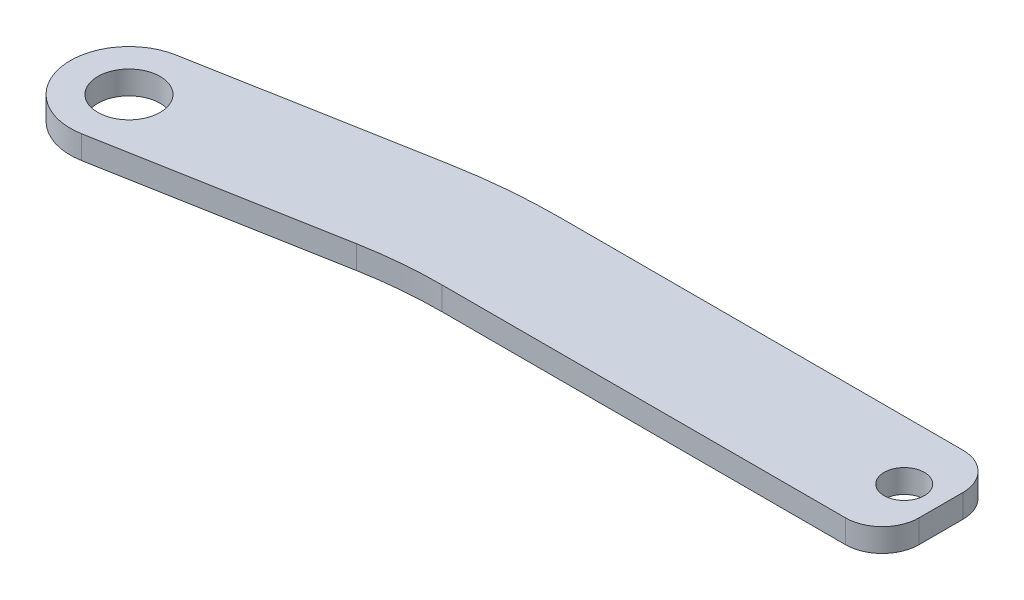
SolidWorks part; units mm, degrees
material "Copper"
ref_plane "Front Plane" through (0, 0, 0) normal (0, 0, 1) x (1, 0, 0)
ref_plane "Top Plane" through (0, 0, 0) normal (0, 1, 0) x (1, 0, 0)
ref_plane "Right Plane" through (0, 0, 0) normal (1, 0, 0) x (0, 0, -1)
sketch "Sketch1" plane through (0, 0, 0) normal (0, 1, 0) x (1, 0, 0)
  line L0 (-1.4287, 7.8714) -> (30.29, 13.6283)
  line L1 (43.8622, 14.85) -> (98.8622, 14.85)
  line L2 (98.8622, -1.15) -> (43.8622, -1.15)
  line L3 (33.1473, -2.1145) -> (1.4287, -7.8714)
  line L4 (103.8622, 3.85) -> (103.8622, 9.85)
  circle A0 centre (0, 0) radius 4.25
  circle A1 centre (98.8622, 6.85) radius 2.75
  arc A5 (1.4287, -7.8714) -> (-1.4287, 7.8714) centre (0, 0) cw
  arc A6 (43.8622, -1.15) -> (33.1473, -2.1145) centre (43.8622, -61.15) ccw
  arc A7 (43.8622, 14.85) -> (30.29, 13.6283) centre (43.8622, -61.15) ccw
  arc A9 (98.8622, -1.15) -> (103.8622, 3.85) centre (98.8622, 3.85) ccw
  arc A10 (103.8622, 9.85) -> (98.8622, 14.85) centre (98.8622, 9.85) ccw
  point P24 (103.8622, 6.85)
  dimension "D1" = 8.5
  dimension "D2" = 5.5
  dimension "D3" = 16
  dimension "D4" = 55
  dimension "D5" = 60
  dimension "D6" = 5
  dimension "D7" = 5
extrude "Boss-Extrude1" add sketch "Sketch1" along normal blind 3.175
